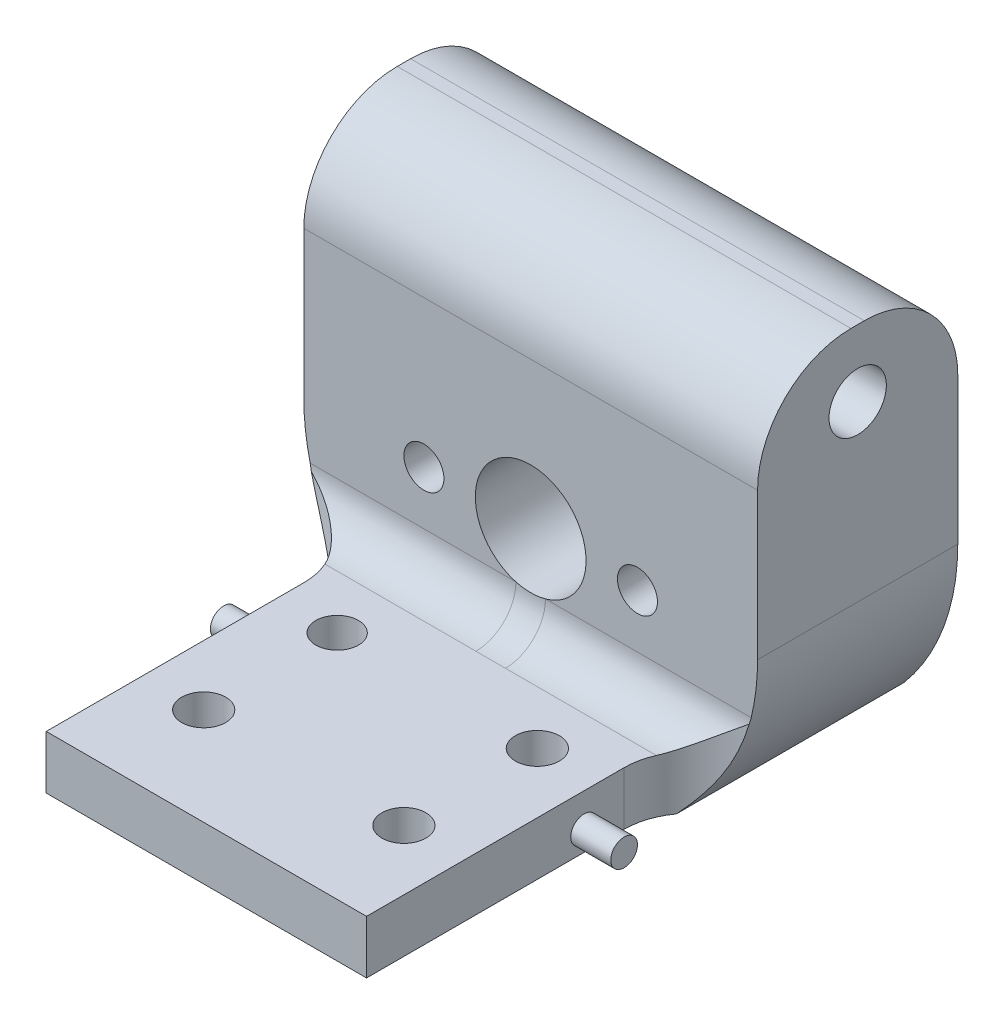
SolidWorks part; units mm, degrees
material "尼龙 101"
ref_plane "Front" through (0, 0, 0) normal (0, 0, 1) x (1, 0, 0)
ref_plane "Top" through (0, 0, 0) normal (0, 1, 0) x (1, 0, 0)
ref_plane "Right" through (0, 0, 0) normal (1, 0, 0) x (0, 0, -1)
sketch "草图1" plane through (0, 0, 0) normal (0, 0, 1) x (1, 0, 0)
  line L0 (-17, 11) -> (17, 11)
  line L1 (-12.9615, -11) -> (12.9615, -11)
  line L2 (17, 0) -> (17, 11)
  line L3 (-17, 0) -> (-17, 11)
  circle A0 centre (0, 0) radius 4.15
  arc A1 (-17, 0) -> (-12.9615, -11) centre (0, 0) ccw
  arc A2 (12.9615, -11) -> (17, 0) centre (0, 0) ccw
  dimension "D1" = 8.3
  dimension "D2" = 34
  dimension "D3" = 11
  dimension "D4" = 11
extrude "凸台-拉伸1" add sketch "草图1" along normal blind 15
sketch "草图2" plane through (17, 0, 0) normal (1, 0, 0) x (0, 0, -1)
  line L1 (-8, 18) -> (-7, 18)
  line L4 (-15, 11) -> (0, 11) construction
  line L5 (-15, 11) -> (0, 11)
  arc A0 (-8, 18) -> (-15, 11) centre (-8, 11) ccw
  arc A1 (0, 11) -> (-7, 18) centre (-7, 11) ccw
  dimension "D2" = 7
extrude "凸台-拉伸7" add sketch "草图2" against normal up to surface (34 mm away) up to face at (-17, 5.5, 7.5)
sketch "草图3" plane through (17, 0, 0) normal (1, 0, 0) x (0, 0, -1)
  line L0 (-7.5, 18) -> (-7.5, 2.2664) construction
  line L1 (-7, 18) -> (-8, 18) construction
  circle A0 centre (-7.5, 13) radius 2.15
  dimension "D1" = 4.3
  dimension "D2" = 5
extrude "切除-拉伸1" cut sketch "草图3" against normal through all
sketch "草图4" plane through (0, 0, 15) normal (0, 0, 1) x (1, 0, 0)
  line L0 (0, 0) -> (0, 5.1) construction
  line L1 (-8, 0) -> (0, 0) construction
  circle A0 centre (-8, 0) radius 1.5
  circle A3 centre (0, 0) radius 8 construction
  circle A7 centre (8, 0) radius 1.5
  circle A8 centre (8, 0) radius 1.5
  point P17 (0, 0)
  dimension "D1" = 3
  dimension "D2" = 16
  dimension "D3" = 2
extrude "切除-拉伸2" cut sketch "草图4" against normal through all
cosmetic thread "装饰螺纹线1" parameters "D2"=4
sketch "草图5" plane through (0, 0, 15) normal (0, 0, 1) x (1, 0, 0)
  line L0 (0, -11) -> (12, -11)
  line L1 (-12.9615, -11) -> (12.9615, -11) construction
  line L2 (12, -11) -> (12, -7)
  line L3 (12, -7) -> (-12, -7)
  line L4 (-12, -7) -> (-12, -11)
  line L5 (-12, -11) -> (0, -11)
  line L9 (0, 0) -> (0, -11) construction
  dimension "D1" = 12
  dimension "D2" = 4
extrude "凸台-拉伸8" add sketch "草图5" along normal blind 72
sketch "草图7" plane through (-12, 0, 0) normal (-1, 0, 0) x (0, 0, 1)
  line L0 (87, -7) -> (15, -7) construction
  line L1 (87, -11) -> (81, -11)
  line L2 (87, -11) -> (87, -7)
  line L3 (87, -7) -> (81, -7)
  line L4 (81, -11) -> (81, -7)
  line L5 (87, -11) -> (15, -11) construction
  line L6 (52, -7) -> (58, -7)
  line L7 (52, -7) -> (52, -11)
  line L8 (52, -11) -> (58, -11)
  line L9 (58, -7) -> (58, -11)
  dimension "D1" = 6
  dimension "D2" = 6
  dimension "D3" = 23
extrude "凸台-拉伸9" add sketch "草图7" along normal blind 12
sketch "草图8" plane through (0, -7, 0) normal (0, 1, 0) x (1, 0, 0)
  line L0 (-24, -58) -> (-12, -58) construction
  line L1 (-24, -52) -> (-21, -52)
  line L2 (-24, -52) -> (-24, -58)
  line L3 (-24, -58) -> (-21, -58)
  line L4 (-21, -52) -> (-21, -58)
  line L5 (12, -87) -> (-24, -87) construction
  line L6 (-24, -81) -> (-21, -81)
  line L7 (-24, -81) -> (-24, -87)
  line L8 (-24, -87) -> (-21, -87)
  line L9 (-21, -81) -> (-21, -87)
  dimension "D1" = 3
extrude "凸台-拉伸10" add sketch "草图8" along normal blind 15
sketch "草图9" plane through (-24, 0, 0) normal (-1, 0, 0) x (0, 0, 1)
  line L1 (55.6, 1.9) -> (58, 1.9) construction
  line L2 (58, -11) -> (58, 8) construction
  line L3 (83.4, 1.9) -> (81, 1.9) construction
  line L4 (81, 8) -> (81, -11) construction
  line L6 (52, 8) -> (58, 8) construction
  circle A0 centre (55.6, 1.9) radius 1.6
  circle A1 centre (83.4, 1.9) radius 1.6
  dimension "D1" = 3.2
  dimension "D3" = 6.1
  dimension "D2" = 27.8
extrude "切除-拉伸4" cut sketch "草图9" against normal through all
sketch "草图6" plane through (0, -7, 0) normal (0, 1, 0) x (1, 0, 0)
  line L0 (0, -74.5) -> (0, -87) construction
  line L1 (7.5, -69.5) -> (12, -69.5) construction
  line L2 (-7.5, -69.5) -> (-12, -69.5) construction
  line L3 (-7.5, -64.5) -> (-7.5, -74.5) construction
  line L4 (-7.5, -74.5) -> (0, -74.5) construction
  line L5 (7.5, -64.5) -> (7.5, -74.5) construction
  line L6 (12, -87) -> (-21, -87) construction
  line L7 (-7.5, -69.5) -> (7.5, -69.5) construction
  line L8 (-12, -81) -> (-12, -58) construction
  line L9 (12, -87) -> (12, -15) construction
  line L10 (7.5, -27) -> (12, -27) construction
  line L11 (-7.5, -27) -> (-12, -27) construction
  line L12 (-7.5, -22) -> (-7.5, -32) construction
  line L13 (-7.5, -32) -> (0, -32) construction
  line L14 (7.5, -22) -> (7.5, -32) construction
  line L15 (-7.5, -27) -> (7.5, -27) construction
  line L16 (-12, -15) -> (-12, -27) construction
  line L17 (-12, -52) -> (-12, -15) construction
  circle A0 centre (-7.5, -74.5) radius 1.55
  circle A1 centre (-7.5, -64.5) radius 1.55
  circle A2 centre (7.5, -64.5) radius 1.55
  circle A3 centre (7.5, -74.5) radius 1.55
  circle A4 centre (-7.5, -32) radius 1.65
  circle A5 centre (-7.5, -22) radius 1.6
  circle A6 centre (7.5, -22) radius 1.65
  circle A7 centre (7.5, -32) radius 1.65
  dimension "D1" = 3.1
  dimension "D2" = 3.1
  dimension "D4" = 12
  dimension "D6" = 3.2
  dimension "D7" = 3.3
  dimension "D8" = 3.3
  dimension "D9" = 3.3
  dimension "D3" = 10
  dimension "D5" = 15
extrude "切除-拉伸3" cut sketch "草图6" against normal through all
sketch "草图11" plane through (-21, 0, 0) normal (1, 0, 0) x (0, 0, -1)
  line L1 (-81.866, 3.9011) -> (-83.4, 4.7868)
  line L2 (-83.4, 4.7868) -> (-85.9, 3.3434)
  line L3 (-85.9, 3.3434) -> (-85.9, 0.4566)
  line L4 (-85.9, 0.4566) -> (-83.4, -0.9868)
  line L5 (-83.4, -0.9868) -> (-81.866, -0.1011)
  line L7 (-81.866, 5.0558) -> (-83.4, 5.9415)
  line L8 (-81, 8) -> (-58, 8) construction
  line L9 (-80.9, 0.4566) -> (-80.9, 1.9)
  line L10 (-69.5, 8) -> (-69.5, -7) construction
  line L11 (-87, -7) -> (-15, -7) construction
  line L12 (-55.6, -0.9868) -> (-57.134, -0.1011)
  line L13 (-53.1, 0.4566) -> (-55.6, -0.9868)
  line L14 (-53.1, 3.3434) -> (-53.1, 0.4566)
  line L15 (-55.6, 4.7868) -> (-53.1, 3.3434)
  line L16 (-57.134, 3.9011) -> (-55.6, 4.7868)
  line L18 (-83.4, 5.9415) -> (-86.9, 3.9207)
  line L19 (-86.9, 3.9207) -> (-86.9, -0.1207)
  line L20 (-86.9, -0.1207) -> (-83.4, -2.1415)
  line L21 (-83.4, -2.1415) -> (-81.866, -1.2558)
  line L22 (-57.134, 5.0558) -> (-55.6, 5.9415)
  line L23 (-55.6, 5.9415) -> (-52.1, 3.9207)
  line L24 (-52.1, 3.9207) -> (-52.1, -0.1207)
  line L25 (-52.1, -0.1207) -> (-55.6, -2.1415)
  line L26 (-55.6, -2.1415) -> (-57.134, -1.2558)
  line L27 (-81.866, 5.0558) -> (-81.866, 3.9011)
  line L29 (-81.866, -0.1011) -> (-81.866, -1.2558)
  line L30 (-57.134, 3.9011) -> (-57.134, 5.0558)
  line L32 (-57.134, -0.1011) -> (-57.134, -1.2558)
  line L33 (-81.366, 4.7671) -> (-83.4, 5.9415) construction
  line L34 (-83.4, -2.1415) -> (-81.366, -0.9671) construction
  line L35 (-57.634, 4.7671) -> (-55.6, 5.9415) construction
  line L36 (-55.6, -2.1415) -> (-57.634, -0.9671) construction
  circle A0 centre (-83.4, 1.9) radius 2.5 construction
  circle A1 centre (-55.6, 1.9) radius 2.5 construction
  dimension "D1" = 5
  dimension "D2" = 1
  dimension "D3" = 1
extrude "凸台-拉伸11" add sketch "草图11" along normal blind 2
sketch "草图12" plane through (0, -7, 0) normal (0, 1, 0) x (1, 0, 0)
  line L1 (-12, -58) -> (-24, -58)
  line L2 (-12, -58) -> (-12, -81)
  line L3 (-12, -81) -> (-24, -81)
  line L4 (-24, -58) -> (-24, -81)
extrude "凸台-拉伸12" add sketch "草图12" against normal up to surface (4 mm away) up to face at (-9.15, -11, 32)
sketch "草图13" plane through (0, 0, 87) normal (0, 0, 1) x (1, 0, 0)
  line L0 (-21, -7) -> (-21, -0.1207)
  line L1 (-21, -0.1207) -> (-19, -0.1207)
  line L3 (12, -4.5) -> (12, -7)
  line L5 (-21, 8) -> (-21, -7) construction
  line L6 (-21, -7) -> (12, -7)
  line L7 (-19, -0.1207) -> (-21, -0.1207) construction
  line L8 (-21, 3.9207) -> (-21, -0.1207) construction
  line L9 (12, -4.5) -> (1, -4.5)
  line L10 (1, -4.5) -> (-19, -0.1207)
  dimension "D1" = 2
  dimension "D2" = 2.5
  dimension "D3" = 11
extrude "凸台-拉伸13" add sketch "草图13" against normal blind 2
sketch "草图14" plane through (0, 0, 52) normal (0, 0, -1) x (-1, 0, 0)
  line L0 (21, -7) -> (21, -0.1207)
  line L1 (21, 8) -> (21, -7) construction
  line L2 (19, -0.1207) -> (21, -0.1207) construction
  line L3 (21, -0.1207) -> (19, -0.1207)
  line L5 (21, -7) -> (-1, -7)
  line L9 (-1, -5) -> (15, -5)
  line L10 (15, -5) -> (19, -0.1207)
  line L11 (-1, -5) -> (-1, -7)
  line L12 (-12, -11) -> (-12, -4.5) construction
  dimension "D1" = 2
  dimension "D2" = 6
  dimension "D3" = 2
  dimension "D4" = 11
extrude "凸台-拉伸14" add sketch "草图14" against normal blind 2
mirror "镜向5" about plane through (0, 0, 0) normal (1, 0, 0) of "凸台-拉伸9"
mirror "镜向6" about plane through (0, 0, 0) normal (1, 0, 0) of "凸台-拉伸10"
mirror "镜向7" about plane through (0, 0, 0) normal (1, 0, 0) of "凸台-拉伸12"
mirror "镜向8" about plane through (0, 0, 0) normal (1, 0, 0) of "凸台-拉伸11"
mirror "镜向9" about plane through (0, 0, 0) normal (1, 0, 0) of "凸台-拉伸13"
mirror "镜向12" about plane through (0, 0, 0) normal (1, 0, 0) of "凸台-拉伸14"
mirror "镜向14" about plane through (0, 0, 0) normal (1, 0, 0) of "切除-拉伸4"
chamfer "倒角3" distance 1 angle 45 16 edges at (0, -7, 85) (0, -7, 54) (22.5, 8, 52) (22.5, 8, 58) (22.5, 8, 81) (22.5, 8, 87) (22.5, -7, 81) (22.5, -7, 58) (21, 5.4986, 82.633) (21, 4.9311, 85.15) (21, -1.6986, 82.633) (21, -1.6986, 56.367) (21, -1.6796, 54.8) (21, 4.9311, 53.85) (21, 5.4986, 56.367) (21, -1.6796, 84.2)
chamfer "倒角4" distance 2 angle 15 1 edges at (0, -5, 52)
sketch "草图16" plane through (-12, 0, 0) normal (-1, 0, 0) x (0, 0, 1)
  line L0 (52, -11) -> (15, -11) construction
  line L1 (15, -11) -> (15, 0) construction
  circle A0 centre (23, -9.5) radius 1
  dimension "D1" = 2
  dimension "D2" = 1.5
  dimension "D3" = 8
extrude "凸台-拉伸16" add sketch "草图16" along normal blind 3
mirror "镜向15" about plane through (0, 0, 0) normal (1, 0, 0) of "凸台-拉伸16"
sketch "草图17" plane through (0, -11, 0) normal (0, -1, 0) x (1, 0, 0)
  line L0 (24, 52) -> (12, 52) construction
  line L1 (20.8522, 52) -> (15.8522, 52)
  line L2 (20.8522, 52) -> (20.8522, 62)
  line L3 (20.8522, 62) -> (15.8522, 62)
  line L4 (15.8522, 52) -> (15.8522, 62)
  dimension "D1" = 5
  dimension "D2" = 10
extrude "凸台-拉伸17" add sketch "草图17" along normal blind 8
sketch "草图18" plane through (20.8522, 0, 0) normal (1, 0, 0) x (0, 0, -1)
  line L0 (-62, -11) -> (-56.3839, -19)
  line L1 (-52, -19) -> (-62, -19) construction
  line L2 (-56.3839, -19) -> (-56, -19)
  line L3 (-52, -15) -> (-52, -15.0487)
  line L4 (-52, -19) -> (-52, -11) construction
  line L5 (-52, -15.0487) -> (-47.9548, -15.6054)
  line L6 (-47.9548, -15.6054) -> (-53.0026, -27)
  line L7 (-53.0026, -27) -> (-66.4386, -22.5461)
  line L8 (-66.4386, -22.5461) -> (-62.3187, -11)
  line L9 (-52, -11) -> (-87, -11) construction
  line L10 (-62.3187, -11) -> (-62, -11)
  arc A0 (-56, -19) -> (-52, -15) centre (-56, -15) ccw
  point P18 (-52, -19)
  dimension "D1" = 4
extrude "切除-拉伸5" cut sketch "草图18" against normal through all
mirror "镜向16" about plane through (0, 0, 0) normal (1, 0, 0) of "切除-拉伸5", "凸台-拉伸17"
sketch "草图19" plane through (0, -7, 0) normal (0, 1, 0) x (1, 0, 0)
  line L1 (-37.218, -39.2982) -> (37.9025, -39.2982)
  line L2 (-37.218, -39.2982) -> (-37.218, -91.1468)
  line L3 (-37.218, -91.1468) -> (37.9025, -91.1468)
  line L4 (37.9025, -39.2982) -> (37.9025, -91.1468)
extrude "切除-拉伸6" cut sketch "草图19" against normal through all both and the other way through all
fillet "圆角1" radius 3 1 edges at (0, -7, 15)
fillet "圆角2" radius 5 2 edges at (-12, -7.5, 15) (12, -7.5, 15)
